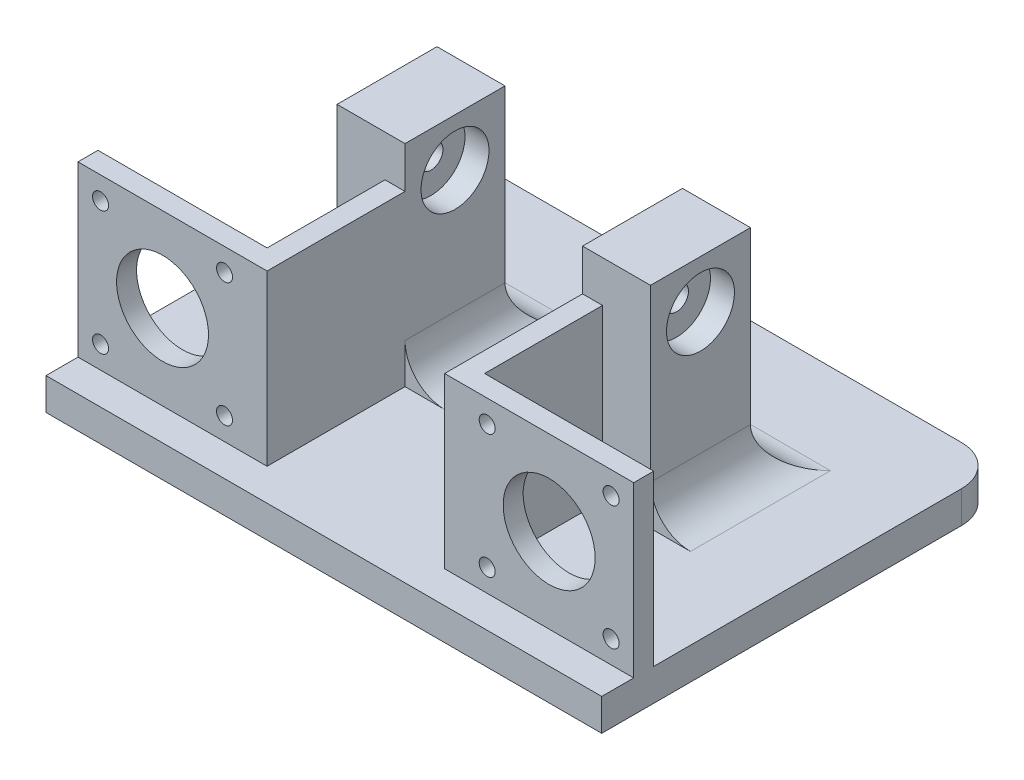
SolidWorks part; units mm, degrees
ref_plane "Alzado" through (0, 0, 0) normal (0, 0, 1) x (1, 0, 0)
ref_plane "Planta" through (0, 0, 0) normal (0, 1, 0) x (1, 0, 0)
ref_plane "Vista lateral" through (0, 0, 0) normal (1, 0, 0) x (0, 0, -1)
sketch "Croquis1" plane through (0, 0, 0) normal (0, 1, 0) x (1, 0, 0)
  circle A0 centre (0, 0) radius 10
  dimension "D1" = 20
extrude "Saliente-Extruir1" add sketch "Croquis1" along normal blind 10
sketch "Croquis3" plane through (0, 0, 0) normal (0, -1, 0) x (1, 0, 0)
  line L1 (62, 15) -> (-77, 15)
  line L2 (62, 15) -> (62, -45)
  line L3 (62, -45) -> (-77, -45)
  line L4 (-77, 15) -> (-77, -45)
  dimension "D1" = 60
  dimension "D2" = 139
  dimension "D3" = 45
  dimension "D4" = 62
extrude "Saliente-Extruir2" add sketch "Croquis3" along normal blind 8
sketch "Croquis2" plane through (0, 10, 0) normal (0, 1, 0) x (1, 0, 0)
  line L0 (2.2361, 2) -> (-2.2361, 2)
  arc A0 (-2.2361, 2) -> (2.2361, 2) centre (0, 0) ccw
  dimension "D1" = 6
  dimension "D2" = 2
extrude "Cortar-Extruir1" cut sketch "Croquis2" against normal up to next
fillet "Redondeo1" radius 3 1 edges at (0, 0, 10) type face fillet first side face at (0, 10, 10) second side face at (0, 0, 10)
sketch "Croquis4" plane through (0, 0, 15) normal (0, 0, 1) x (1, 0, 0)
  line L4 (62, 0) -> (-77, 0)
  line L5 (-77, 0) -> (-77, -8)
  line L6 (-77, -8) -> (62, -8)
  line L7 (62, -8) -> (62, 0)
  line L8 (62, 0) -> (-77, 0)
  line L9 (-77, 0) -> (-77, -8)
  line L10 (-77, -8) -> (62, -8)
  line L11 (62, -8) -> (62, 0)
  dimension "D1" = 0
extrude "Saliente-Extruir3" add sketch "Croquis4" along normal blind 40
sketch "Croquis6" plane through (0, 0, 0) normal (0, 1, 0) x (1, 0, 0)
  line L5 (-46.7, 12.5) -> (-29.7, 12.5)
  line L6 (-46.7, 12.5) -> (-46.7, -12.5)
  line L7 (-46.7, -12.5) -> (-29.7, -12.5)
  line L8 (-29.7, 12.5) -> (-29.7, -12.5)
  line L9 (14.7, 12.5) -> (31.7, 12.5)
  line L10 (14.7, 12.5) -> (14.7, -12.5)
  line L11 (14.7, -12.5) -> (31.7, -12.5)
  line L12 (31.7, 12.5) -> (31.7, -12.5)
  dimension "D1" = 25
  dimension "D2" = 12.5
  dimension "D3" = 17
  dimension "D4" = 17
  dimension "D5" = 25
  dimension "D7" = 14.7
  dimension "D8" = 29.7
extrude "Saliente-Extruir4" add sketch "Croquis6" along normal blind 52.65
sketch "Croquis7" plane through (31.7, 0, 0) normal (1, 0, 0) x (0, 0, -1)
  line L2 (-12.5, 52.65) -> (-12.5, 0) construction
  line L3 (-12.5, 52.65) -> (12.5, 52.65) construction
  circle A0 centre (0, 40.65) radius 3
  dimension "D1" = 6
  dimension "D2" = 12.5
  dimension "D3" = 12
extrude "Cortar-Extruir2" cut sketch "Croquis7" against normal blind 119
sketch "Croquis8" plane through (31.7, 0, 0) normal (1, 0, 0) x (0, 0, -1)
  circle A0 centre (0, 40.65) radius 8.5
  dimension "D1" = 17
extrude "Cortar-Extruir3" cut sketch "Croquis8" against normal blind 6
sketch "Croquis9" plane through (14.7, 0, 0) normal (-1, 0, 0) x (0, 0, 1)
  circle A0 centre (0, 40.65) radius 8.5
  dimension "D1" = 17
extrude "Cortar-Extruir4" cut sketch "Croquis9" against normal blind 6
sketch "Croquis10" plane through (-29.7, 0, 0) normal (1, 0, 0) x (0, 0, -1)
  circle A0 centre (0, 40.65) radius 8.5
  dimension "D1" = 17
extrude "Cortar-Extruir5" cut sketch "Croquis10" against normal blind 6
sketch "Croquis11" plane through (-46.7, 0, 0) normal (-1, 0, 0) x (0, 0, 1)
  circle A0 centre (0, 40.65) radius 8.5
  dimension "D1" = 17
extrude "Cortar-Extruir6" cut sketch "Croquis11" against normal blind 6
sketch "Croquis12" plane through (0, 0, -45) normal (0, 0, -1) x (-1, 0, 0)
  line L0 (77, 0) -> (-62, 0) construction
  circle A0 centre (0, 6) radius 2
  dimension "D1" = 4
  dimension "D2" = 6
extrude "Cortar-Extruir7" cut sketch "Croquis12" against normal blind 79
sketch "Croquis13" plane through (0, 0, 0) normal (0, 1, 0) x (1, 0, 0)
  line L0 (62, 45) -> (62, -55) construction
  line L1 (62, -47) -> (19.7, -47)
  line L2 (62, -47) -> (62, -42)
  line L3 (62, -42) -> (19.7, -42)
  line L4 (19.7, -47) -> (19.7, -42)
  line L5 (-77, -55) -> (-77, 45) construction
  line L6 (-77, -47) -> (-34.7, -47)
  line L7 (-77, -47) -> (-77, -42)
  line L8 (-77, -42) -> (-34.7, -42)
  line L9 (-34.7, -47) -> (-34.7, -42)
  line L10 (62, -55) -> (-77, -55) construction
  dimension "D1" = 5
  dimension "D2" = 42.3
  dimension "D3" = 42.3
  dimension "D4" = 8
  dimension "D5" = 8
extrude "Saliente-Extruir5" add sketch "Croquis13" along normal blind 42.3
sketch "Croquis14" plane through (0, 0, 47) normal (0, 0, 1) x (1, 0, 0)
  line L0 (40.85, 42.3) -> (40.85, 17.188) construction
  line L1 (19.7, 42.3) -> (62, 42.3) construction
  line L2 (19.7, 21.15) -> (42.4958, 21.15) construction
  line L3 (19.7, 42.3) -> (19.7, 0) construction
  line L4 (-55.85, 42.3) -> (-55.85, 9.9453) construction
  line L5 (-77, 42.3) -> (-34.7, 42.3) construction
  line L6 (-77, 21.15) -> (-47.6717, 21.15) construction
  line L7 (-77, 42.3) -> (-77, 0) construction
  line L8 (62, 42.3) -> (62, 0) construction
  circle A0 centre (40.85, 21.15) radius 11.5
  circle A1 centre (25.35, 36.65) radius 2
  circle A2 centre (56.35, 36.65) radius 2
  circle A3 centre (56.35, 5.65) radius 2
  circle A4 centre (25.35, 5.65) radius 2
  circle A5 centre (-55.85, 21.15) radius 11.5
  circle A6 centre (-40.35, 36.65) radius 2
  circle A7 centre (-71.35, 36.65) radius 2
  circle A8 centre (-40.35, 5.65) radius 2
  circle A9 centre (-71.35, 5.65) radius 2
  dimension "D1" = 23
  dimension "D2" = 23
  dimension "D9" = 4
  dimension "D10" = 4
  dimension "D11" = 4
  dimension "D12" = 4
  dimension "D13" = 4
  dimension "D14" = 4
  dimension "D15" = 4
  dimension "D16" = 4
  dimension "D3" = 31
  dimension "D4" = 31
  dimension "D5" = 31
  dimension "D6" = 5.65
  dimension "D7" = 5.65
  dimension "D8" = 5.65
extrude "Cortar-Extruir8" cut sketch "Croquis14" against normal up to next
sketch "Croquis15" plane through (0, -8, 0) normal (0, -1, 0) x (1, 0, 0)
  circle A0 centre (0, 0) radius 41.5
  dimension "D1" = 83
extrude "Cortar-Extruir9" cut sketch "Croquis15" against normal blind 3
fillet "Redondeo2" radius 10 1 edges at (-46.7, 0, 0) type face fillet first side face at (-46.7, 40.65, 8.5) second side face at (0, 0, 13)
fillet "Redondeo3" radius 10 1 edges at (-43.2, 0, -12.5) type face fillet first side face at (-41.4858, 22.6458, -12.5) second side face at (0, 0, 13)
fillet "Redondeo4" radius 10 1 edges at (-29.7, 0, -5) type face fillet first side face at (-29.7, 40.65, -8.5) second side face at (0, 0, 13)
fillet "Redondeo5" radius 10 1 edges at (23.2, 0, -12.5) type face fillet first side face at (23.2, 26.325, -12.5) second side face at (0, 0, 13)
fillet "Redondeo6" radius 10 1 edges at (31.7, 0, -5) type face fillet first side face at (31.7, 40.65, -8.5) second side face at (0, 0, 13)
fillet "Redondeo7" radius 3 1 edges at (14.7, 0, -5) type face fillet first side face at (14.7, 40.65, 8.5) second side face at (0, 0, 13)
sketch "Croquis20" plane through (-34.7, 0, 0) normal (1, 0, 0) x (0, 0, -1)
  line L0 (-12.5, 52.65) -> (-12.5, 10) construction
  line L1 (-47, 0) -> (-12.5, 0)
  line L2 (-47, 0) -> (-47, 42.3)
  line L3 (-47, 42.3) -> (-12.5, 42.3)
  line L4 (-12.5, 0) -> (-12.5, 42.3)
extrude "Saliente-Extruir8" add sketch "Croquis20" along normal blind 5
sketch "Croquis21" plane through (19.7, 0, 0) normal (-1, 0, 0) x (0, 0, 1)
  line L1 (47, 0) -> (12.5, 0)
  line L2 (47, 0) -> (47, 42.3)
  line L3 (47, 42.3) -> (12.5, 42.3)
  line L4 (12.5, 0) -> (12.5, 42.3)
extrude "Saliente-Extruir9" add sketch "Croquis21" along normal blind 5
fillet "Redondeo10" radius 10 1 edges at (-77, -4, -45) type face fillet first side face at (-77, 8.575, 24.75) second side face at (-7.5, -4, -45)
fillet "Redondeo11" radius 10 1 edges at (62, -4, -45) type face fillet first side face at (62, 8.575, 24.75) second side face at (-2.5, -4, -45)
sketch "Croquis18" plane through (0, 10, 0) normal (0, 1, 0) x (1, 0, 0)
  line L1 (-0.5, -3.57) -> (0.5, -3.57)
  line L2 (-0.5, -3.57) -> (-0.5, -8.57)
  line L3 (-0.5, -8.57) -> (0.5, -8.57)
  line L4 (0.5, -3.57) -> (0.5, -8.57)
  dimension "D1" = 0.5
  dimension "D2" = 1
  dimension "D3" = 5
extrude "Cortar-Extruir10" cut sketch "Croquis18" against normal blind 1
